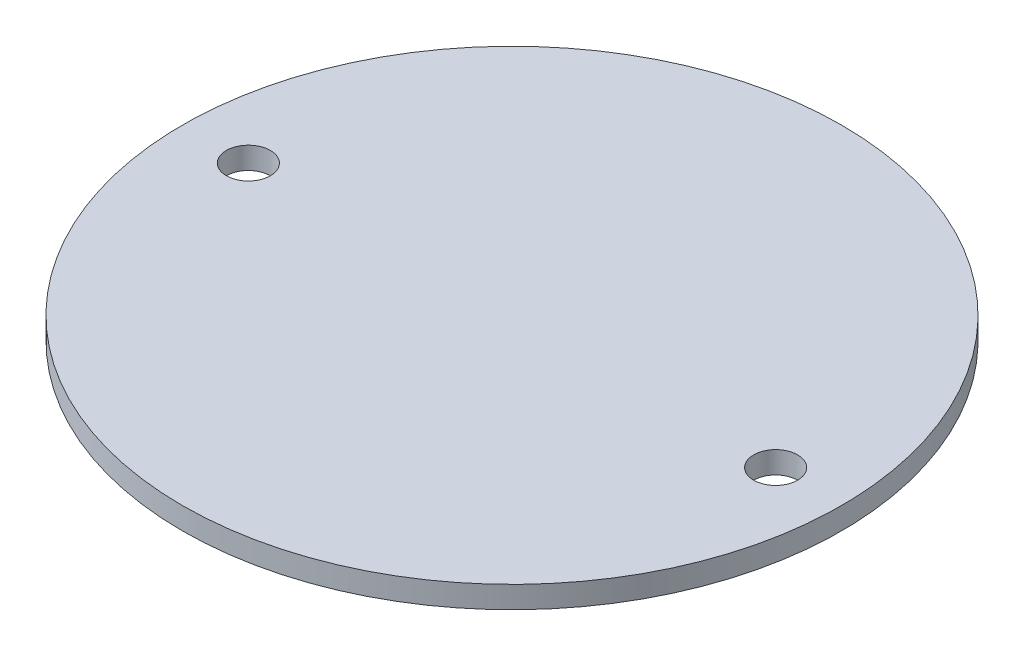
SolidWorks part; units mm, degrees
material "A-Glass Fiber"
ref_plane "Front Plane" through (0, 0, 0) normal (0, 0, 1) x (1, 0, 0)
ref_plane "Top Plane" through (0, 0, 0) normal (0, 1, 0) x (1, 0, 0)
ref_plane "Right Plane" through (0, 0, 0) normal (1, 0, 0) x (0, 0, -1)
sketch "Sketch1" plane through (0, 0, 0) normal (0, 1, 0) x (1, 0, 0)
  circle A0 centre (0, 0) radius 47.625
  dimension "D1" = 95.25
extrude "Boss-Extrude1" add sketch "Sketch1" along normal blind 3.175
extrude "Cut-Extrude1" cut sketch "Sketch2" against normal blind 263.398
sketch "Sketch2" plane through (-55.0397, 231.775, -116.0884) normal (0, 1, 0) x (-1, 0, 0)
  circle A0 centre (-93.1397, 116.0884) radius 3.175
  circle A1 centre (-16.9397, 116.0884) radius 3.175
  point P4 (0, 0)
  point P6 (0, 0)
